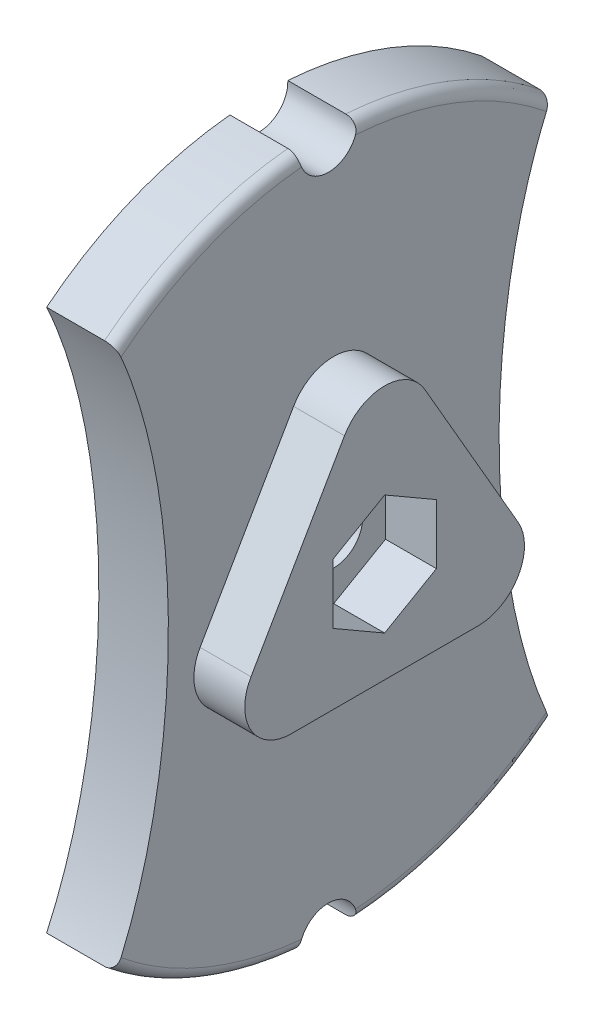
SolidWorks part; units mm, degrees
ref_plane "Front Plane" through (0, 0, 0) normal (0, 0, 1) x (1, 0, 0)
ref_plane "Top Plane" through (0, 0, 0) normal (0, 1, 0) x (1, 0, 0)
ref_plane "Right Plane" through (0, 0, 0) normal (1, 0, 0) x (0, 0, -1)
sketch "Sketch2" plane through (0, 0, 0) normal (1, 0, 0) x (0, 0, -1)
  line L0 (55, 0) -> (-55, 0) construction
  arc A0 (2.5834, -38.0123) -> (2.5834, 38.0123) centre (0, 0) ccw
  circle A1 centre (0, 0) radius 3.175
  arc A2 (-3.7626, -37.9138) -> (2.5834, -38.0123) centre (-0.588, -37.8625) cw
  arc A3 (-3.7626, 37.9138) -> (2.5834, 38.0123) centre (-0.588, 37.8625) ccw
  arc A4 (-3.7626, 37.9138) -> (-3.7626, -37.9138) centre (0, 0) ccw
  point P11 (0, 0)
  point P12 (-0.588, -38.0123)
  point P13 (0, 0)
  point P14 (0, 0)
  dimension "D1" = 76.2
  dimension "D2" = 6.35
  dimension "D3" = 3.175
extrude "Boss-Extrude1" add sketch "Sketch2" along normal blind 7.62
sketch "Sketch3" plane through (7.62, 0, 0) normal (1, 0, 0) x (0, 0, -1)
  line L0 (-5.675, 3.2765) -> (-5.675, -3.2765)
  line L1 (19.05, -10.9985) -> (0, 21.997)
  line L2 (0, 21.997) -> (-19.05, -10.9985)
  line L3 (-19.05, -10.9985) -> (19.05, -10.9985)
  line L4 (5.675, -3.2765) -> (5.675, 3.2765)
  line L5 (5.675, 3.2765) -> (0, 6.5529)
  line L6 (0, 6.5529) -> (-5.675, 3.2765)
  line L7 (-5.675, -3.2765) -> (0, -6.5529)
  line L8 (0, -6.5529) -> (5.675, -3.2765)
  circle A0 centre (0, 0) radius 10.9985 construction
  circle A1 centre (0, 0) radius 5.675 construction
  dimension "D1" = 11.35
  dimension "D2" = 38.1
extrude "Boss-Extrude2" add sketch "Sketch3" along normal blind 5.58
fillet "Fillet1" radius 5.08 3 edges at (10.41, -10.9985, -19.05) (10.41, 21.997, 0) (10.41, -10.9985, 19.05)
fillet "Fillet3" radius 1.27 2 edges at (7.62, 0, -38.1) (7.62, 0, 38.1)
sketch "Sketch4" plane through (0, 0, 0) normal (-1, 0, 0) x (0, 0, 1)
  arc A0 (-2.5834, 38.0123) -> (-2.5834, -38.0123) centre (0, 0) ccw construction
  ellipse E0 centre (-38.1, 0) end of major axis (-38.1, -42.3764) minor radius 19.9746
extrude "Cut-Extrude1" cut sketch "Sketch4" against normal through all
mirror "Mirror1" about plane through (0, 0, 0) normal (0, 0, 1) of "Cut-Extrude1"
